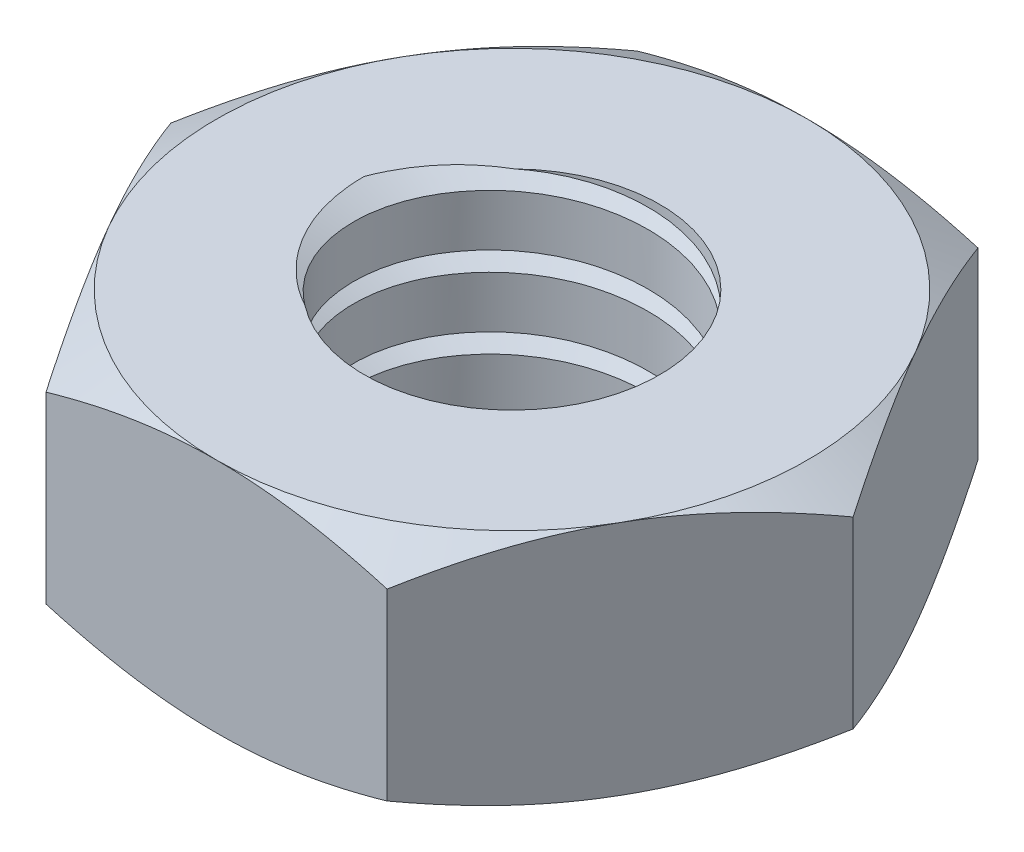
SolidWorks part; units mm, degrees
ref_plane "Front Plane" through (0, 0, 0) normal (0, 0, 1) x (1, 0, 0)
ref_plane "Top Plane" through (0, 0, 0) normal (0, 1, 0) x (1, 0, 0)
ref_plane "Right Plane" through (0, 0, 0) normal (1, 0, 0) x (0, 0, -1)
sketch "Sketch1" plane through (0, 0, 0) normal (0, 1, 0) x (1, 0, 0)
  line L0 (5.7735, 0) -> (2.8868, 5)
  line L1 (-5.7735, 0) -> (-2.8868, -5)
  line L2 (-2.8868, -5) -> (2.8868, -5)
  line L3 (2.8868, -5) -> (5.7735, 0)
  line L4 (2.8868, 5) -> (-2.8868, 5)
  line L5 (-2.8868, 5) -> (-5.7735, 0)
  circle A0 centre (0, 0) radius 5 construction
  dimension "D1" = 10
extrude "Boss-Extrude1" add sketch "Sketch1" along normal blind 4
sketch "Sketch2" plane through (0, 4, 0) normal (0, 1, 0) x (1, 0, 0)
  circle A0 centre (0, 0) radius 5
  circle A1 centre (0, 0) radius 7.7454
extrude "Cut-Extrude3" cut sketch "Sketch2" against normal blind 0.5 draft 60
ref_plane "Plane1" through (0, 2, 0) normal (0, 1, 0) x (1, 0, 0)
mirror "Mirror1" about plane through (0, 2, 0) normal (0, 1, 0) of "Cut-Extrude3"
sketch "Sketch3" plane through (0, 4, 0) normal (0, 1, 0) x (1, 0, 0)
  circle A0 centre (0, 0) radius 2.5
extrude "Cut-Extrude4" cut sketch "Sketch3" against normal blind 7.5
ref_plane "Plane2" through (0, -1, 0) normal (0, -1, 0) x (-1, 0, 0)
sketch "Sketch4" plane through (0, -1, 0) normal (0, -1, 0) x (-1, 0, 0)
  circle A0 centre (0, 0) radius 2.5
curve "Helix/Spiral1" pitch 1.2 height 18 radius 2.5 centre (0, -1, 0) axis (0, 1, 0) start towards (0, 0, -1)
sketch "Sketch5" plane through (0, 0, 0) normal (0, 0, 1) x (1, 0, 0)
  line L0 (-2.4861, -0.98) -> (-2.4861, -0.6433)
  line L1 (-2.4861, -0.6433) -> (-2.937, -0.7742)
  line L2 (-2.937, -0.7742) -> (-2.4861, -0.98)
  spline S0 degree 3 poles (-2.5, -1) (-2.5, -0.9752) (-2.3698, -0.9249) (-1.8138, -0.85) (-0.9816, -0.775) (0, -0.7) (0.9816, -0.625) (1.8138, -0.55) (2.3698, -0.475) (2.5651, -0.4) (2.3698, -0.325) (1.8138, -0.25) (0.7042, -0.15) (-0.7042, -0.05) (-1.8138, 0.05) (-2.3698, 0.125) (-2.5651, 0.2) (-2.3698, 0.275) (-1.8138, 0.35) (-0.7042, 0.45) (0.7042, 0.55) (1.8138, 0.65) (2.3698, 0.725) (2.5651, 0.8) (2.3698, 0.875) (1.8138, 0.95) (0.7042, 1.05) (-0.7042, 1.15) (-1.8138, 1.25) (-2.3698, 1.325) (-2.5651, 1.4) (-2.3698, 1.475) (-1.8138, 1.55) (-0.7042, 1.65) (0.7042, 1.75) (1.8138, 1.85) (2.3698, 1.925) (2.5651, 2) (2.3698, 2.075) (1.8138, 2.15) (0.7042, 2.25) (-0.7042, 2.35) (-1.8138, 2.45) (-2.3698, 2.525) (-2.5651, 2.6) (-2.3698, 2.675) (-1.8138, 2.75) (-0.7042, 2.85) (0.7042, 2.95) (1.8138, 3.05) (2.3698, 3.125) (2.5651, 3.2) (2.3698, 3.275) (1.8138, 3.35) (0.7042, 3.45) (-0.7042, 3.55) (-1.8138, 3.65) (-2.3698, 3.725) (-2.5651, 3.8) (-2.3698, 3.875) (-1.8138, 3.95) (-0.7042, 4.05) (0.7042, 4.15) (1.8138, 4.25) (2.3698, 4.325) (2.5651, 4.4) (2.3698, 4.475) (1.8138, 4.55) (0.7042, 4.65) (-0.7042, 4.75) (-1.8138, 4.85) (-2.3698, 4.925) (-2.5651, 5) (-2.3698, 5.075) (-1.8138, 5.15) (-0.7042, 5.25) (0.7042, 5.35) (1.8138, 5.45) (2.3698, 5.525) (2.5651, 5.6) (2.3698, 5.675) (1.8138, 5.75) (0.7042, 5.85) (-0.7042, 5.95) (-1.8138, 6.05) (-2.3698, 6.125) (-2.5651, 6.2) (-2.3698, 6.275) (-1.8138, 6.35) (-0.7042, 6.45) (0.7042, 6.55) (1.8138, 6.65) (2.3698, 6.725) (2.5651, 6.8) (2.3698, 6.875) (1.8138, 6.95) (0.7042, 7.05) (-0.7042, 7.15) (-1.8138, 7.25) (-2.3698, 7.325) (-2.5651, 7.4) (-2.3698, 7.475) (-1.8138, 7.55) (-0.7042, 7.65) (0.7042, 7.75) (1.8138, 7.85) (2.3698, 7.925) (2.5651, 8) (2.3698, 8.075) (1.8138, 8.15) (0.7042, 8.25) (-0.7042, 8.35) (-1.8138, 8.45) (-2.3698, 8.525) (-2.5651, 8.6) (-2.3698, 8.675) (-1.8138, 8.75) (-0.7042, 8.85) (0.7042, 8.95) (1.8138, 9.05) (2.3698, 9.125) (2.5651, 9.2) (2.3698, 9.275) (1.8138, 9.35) (0.7042, 9.45) (-0.7042, 9.55) (-1.8138, 9.65) (-2.3698, 9.725) (-2.5651, 9.8) (-2.3698, 9.875) (-1.8138, 9.95) (-0.7042, 10.05) (0.7042, 10.15) (1.8138, 10.25) (2.3698, 10.325) (2.5651, 10.4) (2.3698, 10.475) (1.8138, 10.55) (0.7042, 10.65) (-0.7042, 10.75) (-1.8138, 10.85) (-2.3698, 10.925) (-2.5651, 11) (-2.3698, 11.075) (-1.8138, 11.15) (-0.7042, 11.25) (0.7042, 11.35) (1.8138, 11.45) (2.3698, 11.525) (2.5651, 11.6) (2.3698, 11.675) (1.8138, 11.75) (0.7042, 11.85) (-0.7042, 11.95) (-1.8138, 12.05) (-2.3698, 12.125) (-2.5651, 12.2) (-2.3698, 12.275) (-1.8138, 12.35) (-0.7042, 12.45) (0.7042, 12.55) (1.8138, 12.65) (2.3698, 12.725) (2.5651, 12.8) (2.3698, 12.875) (1.8138, 12.95) (0.7042, 13.05) (-0.7042, 13.15) (-1.8138, 13.25) (-2.3698, 13.325) (-2.5651, 13.4) (-2.3698, 13.475) (-1.8138, 13.55) (-0.7042, 13.65) (0.7042, 13.75) (1.8138, 13.85) (2.3698, 13.925) (2.5651, 14) (2.3698, 14.075) (1.8138, 14.15) (0.7042, 14.25) (-0.7042, 14.35) (-1.8138, 14.45) (-2.3698, 14.525) (-2.5651, 14.6) (-2.3698, 14.675) (-1.8138, 14.75) (-0.7042, 14.85) (0.7042, 14.95) (1.8138, 15.05) (2.3698, 15.125) (2.5651, 15.2) (2.3698, 15.275) (1.8138, 15.35) (0.7042, 15.45) (-0.7042, 15.55) (-1.8138, 15.65) (-2.3698, 15.725) (-2.5651, 15.8) (-2.3698, 15.875) (-1.8138, 15.95) (-0.7042, 16.05) (0.7042, 16.15) (1.8138, 16.25) (2.3698, 16.325) (2.5651, 16.4) (2.3698, 16.475) (1.8138, 16.55) (0.9816, 16.625) (0, 16.7) (-0.9816, 16.775) (-1.8138, 16.85) (-2.3698, 16.9249) (-2.5, 16.9752) (-2.5, 17) knots 0 0 0 0 0.004167 0.008333 0.0125 0.016667 0.020833 0.025 0.029167 0.033333 0.0375 0.041667 0.045833 0.054167 0.058333 0.0625 0.066667 0.070833 0.075 0.079167 0.0875 0.091667 0.095833 0.1 0.104167 0.108333 0.1125 0.120833 0.125 0.129167 0.133333 0.1375 0.141667 0.145833 0.154167 0.158333 0.1625 0.166667 0.170833 0.175 0.179167 0.1875 0.191667 0.195833 0.2 0.204167 0.208333 0.2125 0.220833 0.225 0.229167 0.233333 0.2375 0.241667 0.245833 0.254167 0.258333 0.2625 0.266667 0.270833 0.275 0.279167 0.2875 0.291667 0.295833 0.3 0.304167 0.308333 0.3125 0.320833 0.325 0.329167 0.333333 0.3375 0.341667 0.345833 0.354167 0.358333 0.3625 0.366667 0.370833 0.375 0.379167 0.3875 0.391667 0.395833 0.4 0.404167 0.408333 0.4125 0.420833 0.425 0.429167 0.433333 0.4375 0.441667 0.445833 0.454167 0.458333 0.4625 0.466667 0.470833 0.475 0.479167 0.4875 0.491667 0.495833 0.5 0.504167 0.508333 0.5125 0.520833 0.525 0.529167 0.533333 0.5375 0.541667 0.545833 0.554167 0.558333 0.5625 0.566667 0.570833 0.575 0.579167 0.5875 0.591667 0.595833 0.6 0.604167 0.608333 0.6125 0.620833 0.625 0.629167 0.633333 0.6375 0.641667 0.645833 0.654167 0.658333 0.6625 0.666667 0.670833 0.675 0.679167 0.6875 0.691667 0.695833 0.7 0.704167 0.708333 0.7125 0.720833 0.725 0.729167 0.733333 0.7375 0.741667 0.745833 0.754167 0.758333 0.7625 0.766667 0.770833 0.775 0.779167 0.7875 0.791667 0.795833 0.8 0.804167 0.808333 0.8125 0.820833 0.825 0.829167 0.833333 0.8375 0.841667 0.845833 0.854167 0.858333 0.8625 0.866667 0.870833 0.875 0.879167 0.8875 0.891667 0.895833 0.9 0.904167 0.908333 0.9125 0.920833 0.925 0.929167 0.933333 0.9375 0.941667 0.945833 0.954167 0.958333 0.9625 0.966667 0.970833 0.975 0.979167 0.983333 0.9875 0.991667 0.995833 1 1 1 1 construction
sweep "Cut-Sweep1" cut profiles "Sketch5" path "Helix/Spiral1" align with end faces yes
